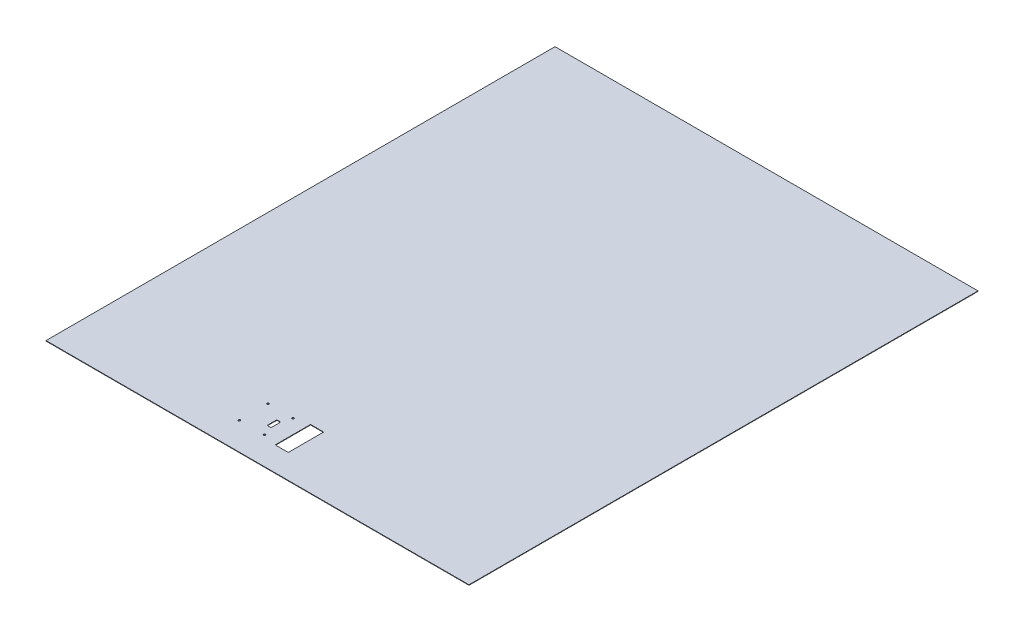
SolidWorks part; units mm, degrees
ref_plane "Front Plane" through (0, 0, 0) normal (0, 0, 1) x (1, 0, 0)
ref_plane "Top Plane" through (0, 0, 0) normal (0, 1, 0) x (1, 0, 0)
ref_plane "Right Plane" through (0, 0, 0) normal (1, 0, 0) x (0, 0, -1)
sketch "Sketch1" plane through (0, 0, 0) normal (0, 1, 0) x (1, 0, 0)
  line L1 (612.6065, -310.951) -> (-259.8935, -310.951)
  line L2 (612.6065, -310.951) -> (612.6065, 739.049)
  line L3 (612.6065, 739.049) -> (-259.8935, 739.049)
  line L4 (-259.8935, -310.951) -> (-259.8935, 739.049)
  dimension "D1" = 1050
  dimension "D2" = 872.5
extrude "Boss-Extrude1" add sketch "Sketch1" along normal blind 1
sketch "Sketch2" plane through (0, 1, 0) normal (0, 1, 0) x (1, 0, 0)
  line L0 (-259.8935, -310.951) -> (612.6065, -310.951) construction
  line L1 (162.8565, -187.951) -> (189.8565, -187.951)
  line L2 (162.8565, -187.951) -> (162.8565, -260.951)
  line L3 (162.8565, -260.951) -> (189.8565, -260.951)
  line L4 (189.8565, -187.951) -> (189.8565, -260.951)
  line L5 (612.6065, -310.951) -> (612.6065, 739.049) construction
  line L6 (-259.8935, 739.049) -> (-259.8935, -310.951) construction
  point P4 (222.6304, 662.2482)
  point P5 (210.4962, -268.4868)
  point P6 (176.3565, -260.951)
  point P9 (189.8565, -224.451)
  dimension "D1" = 27
  dimension "D2" = 73
  dimension "D3" = 50
  dimension "D4" = 422.75
  dimension "D5" = 422.75
extrude "Cut-Extrude1" cut sketch "Sketch2" against normal blind 1
sketch "Sketch3" plane through (0, 1, 0) normal (0, 1, 0) x (1, 0, 0)
  line L0 (189.8565, -187.951) -> (162.8565, -187.951) construction
  line L1 (162.8565, -260.951) -> (189.8565, -260.951) construction
  line L2 (162.8565, -187.951) -> (162.8565, -260.951) construction
  circle A0 centre (133.6565, -194.951) radius 2
  circle A1 centre (133.6565, -253.951) radius 2
  circle A2 centre (81.9765, -194.951) radius 2
  circle A3 centre (81.9765, -253.951) radius 2
  dimension "D1" = 4
  dimension "D2" = 4
  dimension "D3" = 4
  dimension "D4" = 4
  dimension "D5" = 7
  dimension "D6" = 7
  dimension "D7" = 29.2
  dimension "D8" = 29.2
  dimension "D9" = 7
  dimension "D10" = 7
  dimension "D11" = 51.68
  dimension "D12" = 51.68
extrude "Cut-Extrude2" cut sketch "Sketch3" against normal through all
sketch "Sketch4" plane through (0, 1, 0) normal (0, 1, 0) x (1, 0, 0)
  line L1 (127.7565, -214.451) -> (119.7565, -214.451)
  line L2 (127.7565, -214.451) -> (127.7565, -234.451)
  line L3 (127.7565, -234.451) -> (119.7565, -234.451)
  line L4 (119.7565, -214.451) -> (119.7565, -234.451)
  circle A0 centre (133.6565, -194.951) radius 2 construction
  circle A1 centre (133.6565, -253.951) radius 2 construction
  dimension "D1" = 20
  dimension "D2" = 8
  dimension "D3" = 19.5
  dimension "D4" = 19.5
  dimension "D5" = 5.9
extrude "Cut-Extrude3" cut sketch "Sketch4" against normal blind 1
fillet "Fillet1" radius 2 4 edges at (119.7565, 0.5, 214.451) (119.7565, 0.5, 234.451) (127.7565, 0.5, 234.451) (127.7565, 0.5, 214.451)
